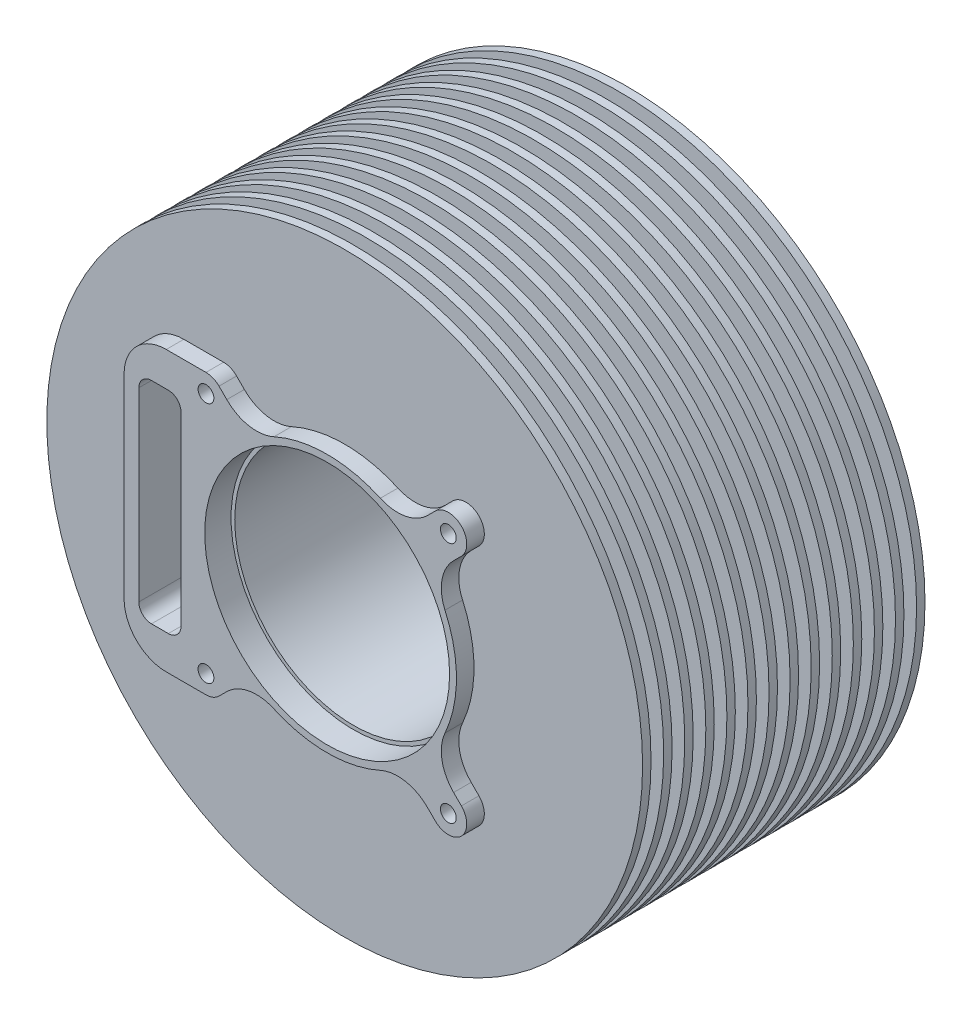
SolidWorks part; units mm, degrees
material "2024-T3"
ref_plane "Front Plane" through (0, 0, 0) normal (0, 0, 1) x (1, 0, 0)
ref_plane "Top Plane" through (0, 0, 0) normal (0, 1, 0) x (1, 0, 0)
ref_plane "Right Plane" through (0, 0, 0) normal (1, 0, 0) x (0, 0, -1)
sketch "Sketch1" plane through (0, 0, 0) normal (0, 0, 1) x (1, 0, 0)
  line L8 (-91.7539, 59.9982) -> (-95.4428, 63.6872)
  line L9 (-107.8172, 51.3128) -> (-104.1282, 47.6239)
  line L10 (-104.1282, -47.6239) -> (-107.8172, -51.3128)
  line L11 (-95.4428, -63.6872) -> (-91.7539, -59.9982)
  line L12 (3.4939, -59.9982) -> (7.1828, -63.6872)
  line L13 (19.5572, -51.3128) -> (15.8682, -47.6239)
  line L14 (15.8682, 47.6239) -> (19.5572, 51.3128)
  line L15 (7.1828, 63.6872) -> (3.4939, 59.9982)
  line L16 (-91.7539, 59.9982) -> (-95.4428, 63.6872)
  line L17 (-107.8172, 51.3128) -> (-104.1282, 47.6239)
  line L18 (-104.1282, -47.6239) -> (-107.8172, -51.3128)
  line L19 (-95.4428, -63.6872) -> (-91.7539, -59.9982)
  line L20 (3.4939, -59.9982) -> (7.1828, -63.6872)
  line L21 (19.5572, -51.3128) -> (15.8682, -47.6239)
  line L22 (15.8682, 47.6239) -> (19.5572, 51.3128)
  line L23 (7.1828, 63.6872) -> (3.4939, 59.9982)
  circle A0 centre (-101.63, -57.5) radius 3.75 construction
  circle A1 centre (13.37, -57.5) radius 3.75 construction
  circle A2 centre (13.37, 57.5) radius 3.75 construction
  circle A3 centre (-44.13, 0) radius 56.35 construction
  circle A4 centre (-101.63, 57.5) radius 3.75 construction
  circle A5 centre (-101.63, -57.5) radius 3.75
  circle A6 centre (13.37, -57.5) radius 3.75
  circle A7 centre (13.37, 57.5) radius 3.75
  circle A8 centre (-44.13, 0) radius 56.35
  circle A9 centre (-101.63, 57.5) radius 3.75
  arc A16 (-91.7539, 59.9982) -> (-69.3802, 55.9129) centre (-77.6117, 74.1404) ccw
  arc A17 (-95.4428, 63.6872) -> (-107.8172, 51.3128) centre (-101.63, 57.5) ccw
  arc A18 (-100.0429, 25.2502) -> (-104.1282, 47.6239) centre (-118.2704, 33.4817) ccw
  arc A19 (-100.0429, 25.2502) -> (-100.0429, -25.2502) centre (-44.13, 0) ccw
  arc A20 (-104.1282, -47.6239) -> (-100.0429, -25.2502) centre (-118.2704, -33.4817) ccw
  arc A21 (-107.8172, -51.3128) -> (-95.4428, -63.6872) centre (-101.63, -57.5) ccw
  arc A22 (-69.3802, -55.9129) -> (-91.7539, -59.9982) centre (-77.6117, -74.1404) ccw
  arc A23 (-69.3802, -55.9129) -> (-18.8798, -55.9129) centre (-44.13, 0) ccw
  arc A24 (3.4939, -59.9982) -> (-18.8798, -55.9129) centre (-10.6483, -74.1404) ccw
  arc A25 (7.1828, -63.6872) -> (19.5572, -51.3128) centre (13.37, -57.5) ccw
  arc A26 (11.7829, -25.2502) -> (15.8682, -47.6239) centre (30.0104, -33.4817) ccw
  arc A27 (11.7829, -25.2502) -> (11.7829, 25.2502) centre (-44.13, 0) ccw
  arc A28 (15.8682, 47.6239) -> (11.7829, 25.2502) centre (30.0104, 33.4817) ccw
  arc A29 (19.5572, 51.3128) -> (7.1828, 63.6872) centre (13.37, 57.5) ccw
  arc A30 (-18.8798, 55.9129) -> (3.4939, 59.9982) centre (-10.6483, 74.1404) ccw
  arc A31 (-18.8798, 55.9129) -> (-69.3802, 55.9129) centre (-44.13, 0) ccw
  arc A32 (-91.7539, 59.9982) -> (-69.3802, 55.9129) centre (-77.6117, 74.1404) ccw
  arc A33 (-95.4428, 63.6872) -> (-107.8172, 51.3128) centre (-101.63, 57.5) ccw
  arc A34 (-100.0429, 25.2502) -> (-104.1282, 47.6239) centre (-118.2704, 33.4817) ccw
  arc A35 (-100.0429, 25.2502) -> (-100.0429, -25.2502) centre (-44.13, 0) ccw
  arc A36 (-104.1282, -47.6239) -> (-100.0429, -25.2502) centre (-118.2704, -33.4817) ccw
  arc A37 (-107.8172, -51.3128) -> (-95.4428, -63.6872) centre (-101.63, -57.5) ccw
  arc A38 (-69.3802, -55.9129) -> (-91.7539, -59.9982) centre (-77.6117, -74.1404) ccw
  arc A39 (-69.3802, -55.9129) -> (-18.8798, -55.9129) centre (-44.13, 0) ccw
  arc A40 (3.4939, -59.9982) -> (-18.8798, -55.9129) centre (-10.6483, -74.1404) ccw
  arc A41 (7.1828, -63.6872) -> (19.5572, -51.3128) centre (13.37, -57.5) ccw
  arc A42 (11.7829, -25.2502) -> (15.8682, -47.6239) centre (30.0104, -33.4817) ccw
  arc A43 (11.7829, -25.2502) -> (11.7829, 25.2502) centre (-44.13, 0) ccw
  arc A44 (15.8682, 47.6239) -> (11.7829, 25.2502) centre (30.0104, 33.4817) ccw
  arc A45 (19.5572, 51.3128) -> (7.1828, 63.6872) centre (13.37, 57.5) ccw
  arc A46 (-18.8798, 55.9129) -> (3.4939, 59.9982) centre (-10.6483, 74.1404) ccw
  arc A47 (-18.8798, 55.9129) -> (-69.3802, 55.9129) centre (-44.13, 0) ccw
  dimension "D1" = 0
extrude "Boss-Extrude1" add sketch "Sketch1" along normal blind 142.33
sketch "Sketch2" plane through (0, 0, 142.33) normal (0, 0, 1) x (1, 0, 0)
  circle A0 centre (-44.13, 0) radius 58.1
  dimension "D1" = 116.2
extrude "Cut-Extrude1" cut sketch "Sketch2" against normal blind 12.5
sketch "Sketch4" plane through (0, 0, 0) normal (0, 0, 1) x (1, 0, 0)
  line L0 (-104.1282, -47.6239) -> (-107.8172, -51.3128) construction
  line L1 (-107.8172, 51.3128) -> (-104.1282, 47.6239) construction
  line L2 (-104.1282, -47.6239) -> (-107.8172, -51.3128)
  line L3 (-107.8172, 51.3128) -> (-104.1282, 47.6239)
  line L4 (-101.63, 66.25) -> (-120.48, 66.25)
  line L5 (-140.48, 46.25) -> (-140.48, -46.25)
  line L6 (-120.48, -66.25) -> (-101.63, -66.25)
  line L8 (-127.48, 50) -> (-119.48, 50)
  line L9 (-133.48, 44) -> (-133.48, -44)
  line L10 (-127.48, -50) -> (-119.48, -50)
  line L11 (-113.48, 44) -> (-113.48, -44)
  arc A0 (-107.8172, -51.3128) -> (-95.4428, -63.6872) centre (-101.63, -57.5) ccw construction
  arc A1 (-104.1282, -47.6239) -> (-100.0429, -25.2502) centre (-118.2704, -33.4817) ccw construction
  arc A2 (-100.0429, 25.2502) -> (-100.0429, -25.2502) centre (-44.13, 0) ccw construction
  arc A3 (-95.4428, 63.6872) -> (-107.8172, 51.3128) centre (-101.63, 57.5) ccw construction
  arc A4 (-100.0429, 25.2502) -> (-104.1282, 47.6239) centre (-118.2704, 33.4817) ccw construction
  arc A5 (-107.8172, -51.3128) -> (-101.63, -66.25) centre (-101.63, -57.5) ccw
  arc A6 (-104.1282, -47.6239) -> (-100.0429, -25.2502) centre (-118.2704, -33.4817) ccw
  arc A7 (-100.0429, 25.2502) -> (-100.0429, -25.2502) centre (-44.13, 0) ccw
  arc A8 (-101.63, 66.25) -> (-107.8172, 51.3128) centre (-101.63, 57.5) ccw
  arc A9 (-100.0429, 25.2502) -> (-104.1282, 47.6239) centre (-118.2704, 33.4817) ccw
  arc A10 (-119.48, -50) -> (-113.48, -44) centre (-119.48, -44) ccw
  arc A11 (-133.48, -44) -> (-127.48, -50) centre (-127.48, -44) ccw
  arc A12 (-119.48, 50) -> (-113.48, 44) centre (-119.48, 44) cw
  arc A13 (-127.48, 50) -> (-133.48, 44) centre (-127.48, 44) ccw
  arc A14 (-140.48, -46.25) -> (-120.48, -66.25) centre (-120.48, -46.25) ccw
  arc A15 (-120.48, 66.25) -> (-140.48, 46.25) centre (-120.48, 46.25) ccw
  point P27 (-113.48, 50)
  point P30 (-133.48, 50)
  point P35 (-133.48, 0)
  point P36 (-140.48, 0)
  point P37 (-105.48, 0)
  dimension "D3" = 6
  dimension "D4" = 20
  dimension "D1" = 100
  dimension "D2" = 20
  dimension "D5" = 35
  dimension "D6" = 7
extrude "Boss-Extrude2" add sketch "Sketch4" along normal blind 142.33
sketch "Sketch5" plane through (0, 0, 0) normal (0, 0, 1) x (1, 0, 0)
  line L0 (-101.63, 66.25) -> (-120.48, 66.25) construction
  line L1 (-91.7539, 59.9982) -> (-95.4428, 63.6872) construction
  line L2 (7.1828, 63.6872) -> (3.4939, 59.9982) construction
  line L3 (15.8682, 47.6239) -> (19.5572, 51.3128) construction
  line L4 (19.5572, -51.3128) -> (15.8682, -47.6239) construction
  line L5 (3.4939, -59.9982) -> (7.1828, -63.6872) construction
  line L6 (-95.4428, -63.6872) -> (-91.7539, -59.9982) construction
  line L7 (-120.48, -66.25) -> (-101.63, -66.25) construction
  line L8 (-140.48, 46.25) -> (-140.48, -46.25) construction
  line L9 (-101.63, 66.25) -> (-120.48, 66.25)
  line L10 (-91.7539, 59.9982) -> (-95.4428, 63.6872)
  line L11 (7.1828, 63.6872) -> (3.4939, 59.9982)
  line L12 (15.8682, 47.6239) -> (19.5572, 51.3128)
  line L13 (19.5572, -51.3128) -> (15.8682, -47.6239)
  line L14 (3.4939, -59.9982) -> (7.1828, -63.6872)
  line L15 (-95.4428, -63.6872) -> (-91.7539, -59.9982)
  line L16 (-120.48, -66.25) -> (-101.63, -66.25)
  line L17 (-140.48, 46.25) -> (-140.48, -46.25)
  line L18 (-127.48, -50) -> (-119.48, -50) construction
  line L19 (-133.48, 44) -> (-133.48, -44) construction
  line L20 (-119.48, 50) -> (-127.48, 50) construction
  line L21 (-113.48, -44) -> (-113.48, 44) construction
  line L22 (-127.48, -50) -> (-119.48, -50)
  line L23 (-133.48, 44) -> (-133.48, -44)
  line L24 (-119.48, 50) -> (-127.48, 50)
  line L25 (-113.48, -44) -> (-113.48, 44)
  arc A0 (-95.4428, 63.6872) -> (-101.63, 66.25) centre (-101.63, 57.5) ccw construction
  arc A1 (-91.7539, 59.9982) -> (-69.3802, 55.9129) centre (-77.6117, 74.1404) ccw construction
  arc A2 (-18.8798, 55.9129) -> (-69.3802, 55.9129) centre (-44.13, 0) ccw construction
  arc A3 (-18.8798, 55.9129) -> (3.4939, 59.9982) centre (-10.6483, 74.1404) ccw construction
  arc A4 (19.5572, 51.3128) -> (7.1828, 63.6872) centre (13.37, 57.5) ccw construction
  arc A5 (15.8682, 47.6239) -> (11.7829, 25.2502) centre (30.0104, 33.4817) ccw construction
  arc A6 (11.7829, -25.2502) -> (11.7829, 25.2502) centre (-44.13, 0) ccw construction
  arc A7 (11.7829, -25.2502) -> (15.8682, -47.6239) centre (30.0104, -33.4817) ccw construction
  arc A8 (7.1828, -63.6872) -> (19.5572, -51.3128) centre (13.37, -57.5) ccw construction
  arc A9 (3.4939, -59.9982) -> (-18.8798, -55.9129) centre (-10.6483, -74.1404) ccw construction
  arc A10 (-69.3802, -55.9129) -> (-18.8798, -55.9129) centre (-44.13, 0) ccw construction
  arc A11 (-69.3802, -55.9129) -> (-91.7539, -59.9982) centre (-77.6117, -74.1404) ccw construction
  arc A12 (-101.63, -66.25) -> (-95.4428, -63.6872) centre (-101.63, -57.5) ccw construction
  arc A13 (-140.48, -46.25) -> (-120.48, -66.25) centre (-120.48, -46.25) ccw construction
  arc A14 (-120.48, 66.25) -> (-140.48, 46.25) centre (-120.48, 46.25) ccw construction
  arc A15 (-95.4428, 63.6872) -> (-101.63, 66.25) centre (-101.63, 57.5) ccw
  arc A16 (-91.7539, 59.9982) -> (-69.3802, 55.9129) centre (-77.6117, 74.1404) ccw
  arc A17 (-18.8798, 55.9129) -> (-69.3802, 55.9129) centre (-44.13, 0) ccw
  arc A18 (-18.8798, 55.9129) -> (3.4939, 59.9982) centre (-10.6483, 74.1404) ccw
  arc A19 (19.5572, 51.3128) -> (7.1828, 63.6872) centre (13.37, 57.5) ccw
  arc A20 (15.8682, 47.6239) -> (11.7829, 25.2502) centre (30.0104, 33.4817) ccw
  arc A21 (11.7829, -25.2502) -> (11.7829, 25.2502) centre (-44.13, 0) ccw
  arc A22 (11.7829, -25.2502) -> (15.8682, -47.6239) centre (30.0104, -33.4817) ccw
  arc A23 (7.1828, -63.6872) -> (19.5572, -51.3128) centre (13.37, -57.5) ccw
  arc A24 (3.4939, -59.9982) -> (-18.8798, -55.9129) centre (-10.6483, -74.1404) ccw
  arc A25 (-69.3802, -55.9129) -> (-18.8798, -55.9129) centre (-44.13, 0) ccw
  arc A26 (-69.3802, -55.9129) -> (-91.7539, -59.9982) centre (-77.6117, -74.1404) ccw
  arc A27 (-101.63, -66.25) -> (-95.4428, -63.6872) centre (-101.63, -57.5) ccw
  arc A28 (-140.48, -46.25) -> (-120.48, -66.25) centre (-120.48, -46.25) ccw
  arc A29 (-120.48, 66.25) -> (-140.48, 46.25) centre (-120.48, 46.25) ccw
  arc A30 (-119.48, -50) -> (-113.48, -44) centre (-119.48, -44) ccw construction
  arc A31 (-133.48, -44) -> (-127.48, -50) centre (-127.48, -44) ccw construction
  arc A32 (-127.48, 50) -> (-133.48, 44) centre (-127.48, 44) ccw construction
  arc A33 (-113.48, 44) -> (-119.48, 50) centre (-119.48, 44) ccw construction
  circle A34 centre (13.37, -57.5) radius 3.75 construction
  circle A35 centre (-101.63, -57.5) radius 3.75 construction
  circle A36 centre (13.37, 57.5) radius 3.75 construction
  circle A37 centre (-101.63, 57.5) radius 3.75 construction
  arc A38 (-119.48, -50) -> (-113.48, -44) centre (-119.48, -44) ccw
  arc A39 (-133.48, -44) -> (-127.48, -50) centre (-127.48, -44) ccw
  arc A40 (-127.48, 50) -> (-133.48, 44) centre (-127.48, 44) ccw
  arc A41 (-113.48, 44) -> (-119.48, 50) centre (-119.48, 44) ccw
  circle A42 centre (13.37, -57.5) radius 3.75
  circle A43 centre (-101.63, -57.5) radius 3.75
  circle A44 centre (13.37, 57.5) radius 3.75
  circle A45 centre (-101.63, 57.5) radius 3.75
  circle A46 centre (-44.13, 0) radius 56.35 construction
  circle A47 centre (-44.13, 0) radius 56.35
  circle A48 centre (-44.13, 0) radius 141.35
  dimension "D1" = 80
extrude "Boss-Extrude3" add sketch "Sketch5" along normal blind 4 contours A48 A29 L9 A15 L10 A16 A17 A18 L11 A19 L12 A20 A21 A22 L13 A23 L14 A24 A25 A26 L15 A27 L16 A28 L17 region at (-181.482, 0, 0)
pattern_linear "LPattern1" count 14 spacing 10 along (0, 0, 1) of "Boss-Extrude3"
sketch "Sketch3" plane through (0, 0, 0) normal (0, 0, 1) x (1, 0, 0)
  circle A0 centre (-44.13, 0) radius 171.35
  arc A1 (-18.8798, 55.9129) -> (-69.3802, 55.9129) centre (-44.13, 0) ccw construction
  circle A2 centre (-44.13, 0) radius 56.35 construction
  circle A3 centre (-101.63, -57.5) radius 3.75 construction
  circle A4 centre (13.37, -57.5) radius 3.75 construction
  circle A5 centre (13.37, 57.5) radius 3.75 construction
  circle A6 centre (-101.63, 57.5) radius 3.75 construction
  circle A7 centre (-44.13, 0) radius 56.35
  circle A8 centre (-101.63, -57.5) radius 3.75
  circle A9 centre (13.37, -57.5) radius 3.75
  circle A10 centre (13.37, 57.5) radius 3.75
  circle A11 centre (-101.63, 57.5) radius 3.75
  dimension "D1" = 110
equation "\"Cylinder Length\"= 169.33"
equation "\"Liner Offset\"= 27"
equation "\"D1@Boss-Extrude1\"=\"Cylinder Length\"-\"Liner Offset\""
equation "\"D1@Sketch2\"=118.2-2"
equation "\"f\"= 118.2 + 2"
